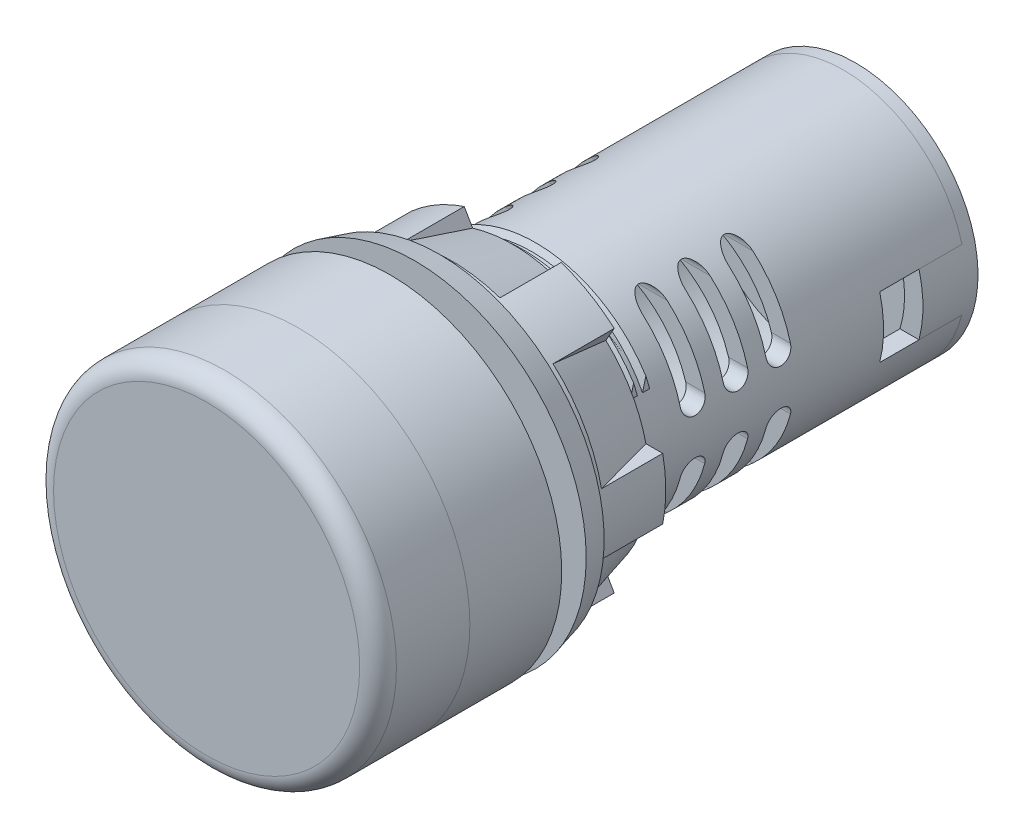
SolidWorks part; units mm, degrees
note: '?' marks a value the reader was unsure of. The reader was unsure of these and kept them because the rebuilt part matched: shared geometry of "Croquis14<4>".
material "PVC Rígido"
ref_plane "Alzado" through (0, 0, 0) normal (0, 0, 1) x (1, 0, 0)
ref_plane "Planta" through (0, 0, 0) normal (0, 1, 0) x (1, 0, 0)
ref_plane "Vista lateral" through (0, 0, 0) normal (1, 0, 0) x (0, 0, -1)
sketch "Croquis1" plane through (0, 0, 0) normal (1, 0, 0) x (0, 0, -1)
  line L0 (7.5, 10) -> (44.5, 10)
  line L1 (0, 0) -> (7.5, 0)
  line L2 (0, 0) -> (0, 14)
  line L3 (0, 14) -> (7.5, 14)
  line L4 (7.5, 10) -> (7.5, 14)
  line L5 (44.5, 10) -> (44.5, 0)
  line L6 (44.5, 0) -> (7.5, 0)
  dimension "D1" = 7.5
  dimension "D2" = 14
  dimension "D3" = 37
  dimension "D4" = 10
revolve "Revolución1" add sketch "Croquis1" angle 360 about L6
shell "Vaciado1" thickness 1.5
sketch "Croquis2" plane through (0, 0, 0) normal (1, 0, 0) x (0, 0, -1)
  line L0 (26, 10) -> (26, -10) construction
  line L1 (44.5, 10) -> (7.5, 10) construction
  line L2 (7.5, -10) -> (44.5, -10) construction
  line L3 (44.5, 0) -> (7.5, 0) construction
  line L4 (44.5, -10) -> (44.5, 10) construction
  line L5 (7.5, -10) -> (7.5, 10) construction
  line L6 (26, 7.5) -> (26, 2.5) construction
  line L7 (27, 7.5) -> (27, 2.5)
  line L8 (25, 7.5) -> (25, 2.5)
  line L9 (29.5, 7.5) -> (29.5, 2.5) construction
  line L10 (30.5, 7.5) -> (30.5, 2.5)
  line L11 (28.5, 7.5) -> (28.5, 2.5)
  line L12 (29.5, -2.5) -> (29.5, -7.5) construction
  line L13 (30.5, -2.5) -> (30.5, -7.5)
  line L14 (28.5, -2.5) -> (28.5, -7.5)
  line L16 (44.5, 2.5) -> (37.7873, 2.5)
  line L17 (44.5, 2.5) -> (44.5, -2.5)
  line L18 (26, 7.5) -> (29.5, 7.5) construction
  line L19 (22.5, 7.5) -> (22.5, 2.5) construction
  line L20 (23.5, 7.5) -> (23.5, 2.5)
  line L21 (21.5, 7.5) -> (21.5, 2.5)
  line L22 (22.5, -2.5) -> (22.5, -7.5) construction
  line L23 (23.5, -2.5) -> (23.5, -7.5)
  line L24 (21.5, -2.5) -> (21.5, -7.5)
  line L25 (26, -2.5) -> (26, -7.5) construction
  line L26 (27, -2.5) -> (27, -7.5)
  line L27 (25, -2.5) -> (25, -7.5)
  line L28 (26, 7.5) -> (22.5, 7.5) construction
  line L29 (44.5, -2.5) -> (37.7873, -2.5)
  line L30 (37.7873, 2.5) -> (37.7873, -2.5)
  line L56 (26, -2.5) -> (26, -7.5) construction
  line L57 (27, -2.5) -> (27, -7.5)
  line L58 (25, -2.5) -> (25, -7.5)
  line L59 (26, -2.5) -> (26, -7.5) construction
  line L60 (27, -2.5) -> (27, -7.5)
  line L61 (25, -2.5) -> (25, -7.5)
  arc A0 (27, 7.5) -> (25, 7.5) centre (26, 7.5) ccw
  arc A1 (25, 2.5) -> (27, 2.5) centre (26, 2.5) ccw
  arc A2 (30.5, 7.5) -> (28.5, 7.5) centre (29.5, 7.5) ccw
  arc A3 (28.5, 2.5) -> (30.5, 2.5) centre (29.5, 2.5) ccw
  arc A4 (30.5, -2.5) -> (28.5, -2.5) centre (29.5, -2.5) ccw
  arc A5 (28.5, -7.5) -> (30.5, -7.5) centre (29.5, -7.5) ccw
  arc A8 (23.5, 7.5) -> (21.5, 7.5) centre (22.5, 7.5) ccw
  arc A9 (21.5, 2.5) -> (23.5, 2.5) centre (22.5, 2.5) ccw
  arc A10 (23.5, -2.5) -> (21.5, -2.5) centre (22.5, -2.5) ccw
  arc A11 (21.5, -7.5) -> (23.5, -7.5) centre (22.5, -7.5) ccw
  arc A12 (27, -2.5) -> (25, -2.5) centre (26, -2.5) ccw
  arc A13 (25, -7.5) -> (27, -7.5) centre (26, -7.5) ccw
  arc A34 (27, -2.5) -> (25, -2.5) centre (26, -2.5) ccw
  arc A35 (25, -7.5) -> (27, -7.5) centre (26, -7.5) ccw
  point P14 (26, 5)
  point P23 (29.5, 5)
  point P30 (29.5, -5)
  point P44 (26, -5)
  point P47 (22.5, 5)
  point P54 (22.5, -5)
  point P61 (26, -5)
  point P74 (26, -5)
  point P81 (26, -5)
  point P88 (26, -5)
  point P95 (26, -5)
  point P102 (26, -5)
  point P109 (26, -5)
  point P116 (26, -5)
  point P123 (26, -5)
  point P130 (26, -5)
  point P137 (26, -5)
  dimension "D3" = 1
  dimension "D1" = 5
  dimension "D2" = 5
  dimension "D6" = 3.5
  dimension "D9" = 3.5
  dimension "D10" = 5
  dimension "D4" = 2
  dimension "D5" = 2
  dimension "D7" = 2
  dimension "D8" = 2
extrude "Cortar-Extruir1" cut sketch "Croquis2" against normal through all both and the other way through all
sketch "Croquis14" plane through (0, 0, -44.5) normal (0, 0, -1) x (-1, 0, 0)
  line L0 (9.6825, 2.5) -> (8.124, 2.5) construction
  line L1 (8.124, -2.5) -> (9.6825, -2.5) construction
  line L2 (-9.6825, -2.5) -> (-8.124, -2.5) construction
  line L3 (-8.124, 2.5) -> (-9.6825, 2.5) construction
  line L4 (9.6825, 2.5) -> (8.124, 2.5)
  line L5 (8.124, -2.5) -> (9.6825, -2.5)
  line L6 (-9.6825, -2.5) -> (-8.124, -2.5)
  line L7 (-8.124, 2.5) -> (-9.6825, 2.5)
  circle A0 centre (0, 0) radius 10 construction
  circle A1 centre (0, 0) radius 10
  arc A2 (9.6825, -2.5) -> (9.6825, 2.5) centre (0, 0) ccw construction
  arc A3 (8.124, -2.5) -> (8.124, 2.5) centre (0, 0) ccw construction
  arc A4 (-9.6825, 2.5) -> (-9.6825, -2.5) centre (0, 0) ccw construction
  arc A5 (-8.124, 2.5) -> (-8.124, -2.5) centre (0, 0) ccw construction
  arc A6 (9.6825, -2.5) -> (9.6825, 2.5) centre (0, 0) ccw
  arc A7 (8.124, -2.5) -> (8.124, 2.5) centre (0, 0) ccw
  arc A8 (-9.6825, 2.5) -> (-9.6825, -2.5) centre (0, 0) ccw
  arc A9 (-8.124, 2.5) -> (-8.124, -2.5) centre (0, 0) ccw
  circle A10 centre (-5, 0) radius 2.5
  circle A11 centre (5, 0) radius 2.5
  line M1 (-9.6825, 2.5) -> (9.6825, 2.5)
  arc M2 (9.6825, 2.5) -> (-9.6825, 2.5) centre (0, 0) ccw
  dimension "D1" = 5
  dimension "D2" = 5
extrude "Saliente-Extruir3" add sketch "Croquis14" along normal blind 1 separate body contours A9 A1 L6 M1 | M2 M1 | A9 L6 A1 L5 A7 M1 | A7 L5 A1 M1
extrude "Saliente-Extruir4" add sketch "Croquis14<4>" against normal blind 3.5 contours A9 A1 L6 M1 | A7 L5 A1 M1
sketch "Croquis14<4>" plane through (0, 0, -44.5) normal (0, 0, -1) x (-1, 0, 0) same geometry as "Croquis14"
ref_plane "Plano1" through (0, 0, -41.5) normal (0, 0, -1) x (-1, 0, 0)
sketch "Croquis4" plane through (0, 0, -41.5) normal (0, 0, -1) x (-1, 0, 0)
  arc A3 (8.124, -2.5) -> (8.124, 2.5) centre (0, 0) ccw construction
  arc A4 (-8.124, -2.5) -> (8.124, -2.5) centre (0, 0) ccw construction
  arc A5 (-8.124, 2.5) -> (-8.124, -2.5) centre (0, 0) ccw construction
  arc A6 (8.124, 2.5) -> (-8.124, 2.5) centre (0, 0) ccw construction
  arc A7 (8.124, -2.5) -> (8.124, 2.5) centre (0, 0) ccw
  arc A8 (-8.124, -2.5) -> (8.124, -2.5) centre (0, 0) ccw
  arc A9 (-8.124, 2.5) -> (-8.124, -2.5) centre (0, 0) ccw
  arc A10 (8.124, 2.5) -> (-8.124, 2.5) centre (0, 0) ccw
extrude "Saliente-Extruir1" add sketch "Croquis4" along normal blind 2.5
ref_plane "Plano2" through (0, 0, -19.5) normal (0, 0, -1) x (-1, 0, 0)
sketch "Croquis6" plane through (0, 0, -19.5) normal (0, 0, -1) x (-1, 0, 0)
  circle A0 centre (0, 0) radius 10
  dimension "D1" = 20
sketch "Croquis9" plane through (0, 0, 0) normal (1, 0, 0) x (0, 0, -1)
  line L0 (19.5, 10) -> (19.2113, 10.5)
  line L1 (19.5, -15.4) -> (19.5, 15.4) construction
  line L2 (44.5, 10) -> (7.5, 10) construction
  line L3 (19.2113, 10.5) -> (18.9226, 10)
  line L4 (18.9226, 10) -> (19.5, 10)
  point P6 (19.2113, 10)
  dimension "D1" = 60
  dimension "D2" = 60
  dimension "D3" = 0.5
curve "Hélice/Espiral1" pitch 1 height 12 turns 12
sweep "Barrer1" add profiles "Croquis9" path "Hélice/Espiral1"
sketch "Croquis10" plane through (0, 0, -7.5) normal (0, 0, -1) x (-1, 0, 0)
  line L0 (-14, 0) -> (14, 0) construction
  line L1 (0, 14) -> (0, -14) construction
  line L2 (-9, -6) -> (-9, -4.3589)
  line L3 (-9, 6) -> (-11, 6)
  line L4 (-11, 6) -> (-11, -6)
  line L5 (-11, -6) -> (-9, -6)
  line L6 (-9, 4.3589) -> (-9, 6)
  line L7 (9, 6) -> (11, 6)
  line L8 (11, 6) -> (11, -6)
  line L9 (11, -6) -> (9, -6)
  line L10 (9, -6) -> (9, -4.3589)
  line L11 (9, 4.3589) -> (9, 6)
  circle A0 centre (0, 0) radius 10 construction
  arc A1 (-9, 4.3589) -> (-9, -4.3589) centre (0, 0) ccw
  arc A2 (9, 4.3589) -> (9, -4.3589) centre (0, 0) cw
  circle A3 centre (0, 0) radius 14 construction
  dimension "D1" = 9
  dimension "D2" = 12
  dimension "D3" = 2
extrude "Cortar-Extruir3" cut sketch "Croquis10" along normal through all
sketch "Croquis11" plane through (0, 0, 0) normal (0, 0, 1) x (1, 0, 0)
  circle A0 centre (0, 0) radius 14 construction
  circle A1 centre (0, 0) radius 14
extrude "Saliente-Extruir2" add sketch "Croquis11" along normal blind 7.5 separate body
shell "Vaciado5" thickness 1.5
fillet "Redondeo1" radius 1.5 1 edges at (14, 0, 7.5)
ref_plane "Plano3" through (0, 0, -9.5) normal (0, 0, -1) x (-1, 0, 0)
sketch "Croquis15" plane through (0, 0, -9.5) normal (0, 0, -1) x (-1, 0, 0)
  circle A0 centre (0, 0) radius 10 construction
  circle A1 centre (0, 0) radius 10
  circle A2 centre (0, 0) radius 14
  dimension "D1" = 4
extrude "Saliente-Extruir6" add sketch "Croquis15" along normal blind 2 separate body
sketch "Croquis16" plane through (0, 0, -11.5) normal (0, 0, -1) x (-1, 0, 0)
  circle A0 centre (0, 0) radius 10 construction
  circle A1 centre (0, 0) radius 10
  circle A2 centre (0, 0) radius 12.5
  dimension "D1" = 2.5
extrude "Saliente-Extruir7" add sketch "Croquis16" along normal blind 6
chamfer "Chaflán1" distance 2 angle 15 1 edges at (0, 14, -11.5)
chamfer "Chaflán2" distance 5 angle 15 1 edges at (0, 12.5, -17.5)
sketch "Croquis17" plane through (0, 0, -17.5) normal (0, 0, -1) x (-1, 0, 0)
  circle A1 centre (0, 0) radius 10.5
  dimension "D1" = 21
sketch "Croquis19" plane through (0, 0, 0) normal (1, 0, 0) x (0, 0, -1)
  line L0 (17.2113, 10) -> (17.5, 10.5)
  line L1 (17.5, 10.5) -> (16.9226, 10.5)
  line L2 (16.9226, 10.5) -> (17.2113, 10)
  line L5 (17.5, -11.1603) -> (17.5, 11.1603) construction
  line L6 (17.5, 10) -> (9.5, 10) construction
  dimension "D1" = 60
  dimension "D2" = 60
  dimension "D3" = 0.5
curve "Hélice/Espiral3" pitch 1 height 9 turns 9
sketch "Croquis20" plane through (0, 0, -11.5) normal (0, 0, -1) x (-1, 0, 0)
  line L0 (-11.1603, 0) -> (-12.5, 0) construction
  line L1 (-3.9587, 11.8566) -> (-3.2733, 10.6694)
  line L2 (-12.2474, -2.5) -> (-10.8766, -2.5)
  line L3 (-8.2888, 9.3566) -> (-7.6034, 8.1694)
  line L4 (-12.2474, 2.5) -> (-10.8766, 2.5)
  line L5 (8.2888, 9.3566) -> (7.6034, 8.1694)
  line L6 (3.9587, 11.8566) -> (3.2733, 10.6694)
  line L7 (12.2474, -2.5) -> (10.8766, -2.5)
  line L8 (12.2474, 2.5) -> (10.8766, 2.5)
  line L9 (3.9587, -11.8566) -> (3.2733, -10.6694)
  line L10 (8.2888, -9.3566) -> (7.6034, -8.1694)
  line L11 (-8.2888, -9.3566) -> (-7.6034, -8.1694)
  line L12 (-3.9587, -11.8566) -> (-3.2733, -10.6694)
  circle A0 centre (0, 0) radius 11.1603 construction
  circle A1 centre (0, 0) radius 12.5 construction
  arc A2 (-10.8766, 2.5) -> (-10.8766, -2.5) centre (0, 0) ccw
  arc A3 (-3.2733, 10.6694) -> (-7.6034, 8.1694) centre (0, 0) ccw
  arc A4 (-3.9587, 11.8566) -> (-8.2888, 9.3566) centre (0, 0) ccw
  arc A5 (7.6034, 8.1694) -> (3.2733, 10.6694) centre (0, 0) ccw
  arc A6 (8.2888, 9.3566) -> (3.9587, 11.8566) centre (0, 0) ccw
  arc A7 (10.8766, -2.5) -> (10.8766, 2.5) centre (0, 0) ccw
  arc A9 (12.2474, -2.5) -> (12.2474, 2.5) centre (0, 0) ccw
  arc A10 (-12.2474, 2.5) -> (-12.2474, -2.5) centre (0, 0) ccw
  arc A11 (3.2733, -10.6694) -> (7.6034, -8.1694) centre (0, 0) ccw
  arc A12 (3.9587, -11.8566) -> (8.2888, -9.3566) centre (0, 0) ccw
  arc A13 (-7.6034, -8.1694) -> (-3.2733, -10.6694) centre (0, 0) ccw
  arc A14 (-8.2888, -9.3566) -> (-3.9587, -11.8566) centre (0, 0) ccw
  point P7 (-11.8301, 0)
  point P32 (0, 0)
  dimension "D1" = 5
  dimension "D3" = 2.5
extrude "Saliente-Extruir9" add sketch "Croquis20" along normal blind 6
sketch "Croquis21" plane through (0, 0, -45.5) normal (0, 0, -1) x (-1, 0, 0)
  point P0 (-5, 0)
  point P1 (5, 0)
sketch "2_1_Point" plane through (0, 0, -45.5) normal (0, 0, -1) x (-1, 0, 0)
  point P0 (-5, 0)
other "2_1" parameters "Diámetro"=2, "Longitud de terminal"=2
ref_axis "Eje1" through (5, 0, -55.5) along (0, 0, 1)?
sketch "2_2_Point" plane through (0, 0, -45.5) normal (0, 0, -1) x (-1, 0, 0)
  point P0 (5, 0)
other "2_2" parameters "Diámetro"=2, "Longitud de terminal"=2
ref_axis "Eje2" through (-5, 0, -55.5) along (0, 0, 1)?
equation "\"D2@Croquis14\"=\"D1@Croquis14\""
